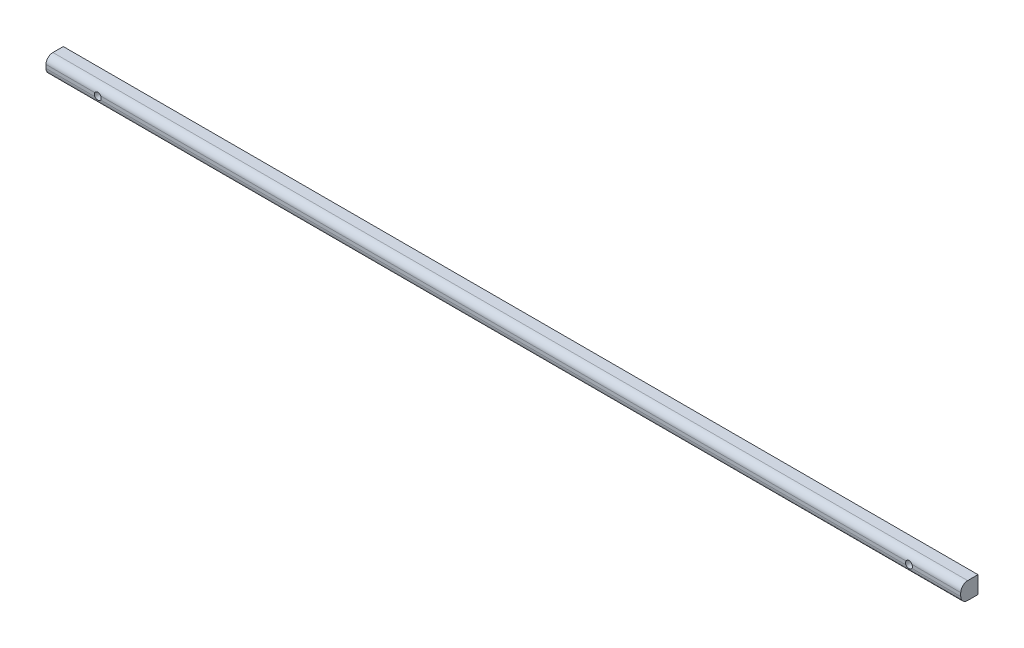
SolidWorks part; units mm, degrees
ref_plane "Front Plane" through (0, 0, 0) normal (0, 0, 1) x (1, 0, 0)
ref_plane "Top Plane" through (0, 0, 0) normal (0, 1, 0) x (1, 0, 0)
ref_plane "Right Plane" through (0, 0, 0) normal (1, 0, 0) x (0, 0, -1)
sketch "Sketch1" plane through (0, 0, 0) normal (0, 0, 1) x (1, 0, 0)
  line L1 (0, 0) -> (-265, 0)
  line L2 (0, 0) -> (0, 5)
  line L3 (0, 5) -> (-265, 5)
  line L4 (-265, 0) -> (-265, 5)
  dimension "D1" = 265
  dimension "D2" = 5
extrude "Boss-Extrude1" add sketch "Sketch1" along normal blind 5
sketch "Sketch2" plane through (0, 0, 5) normal (0, 0, 1) x (1, 0, 0)
  line L0 (-265, 5) -> (-265, 0) construction
  line L1 (-132.5, 5) -> (-132.5, 0) construction
  line L2 (0, 5) -> (-265, 5) construction
  line L3 (-265, 0) -> (0, 0) construction
  circle A0 centre (-250, 2.5) radius 1
  circle A1 centre (-15, 2.5) radius 1
  dimension "D1" = 2
  dimension "D2" = 15
extrude "Cut-Extrude1" cut sketch "Sketch2" against normal through all
fillet "Fillet1" radius 2 2 edges at (-132.5, 0, 5) (-132.5, 5, 5)
